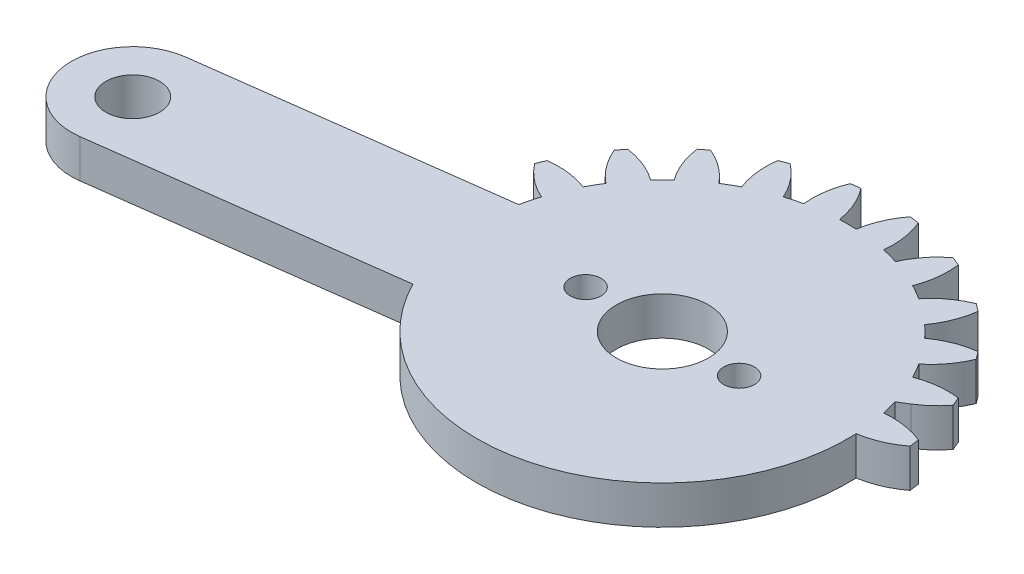
SolidWorks part; units mm, degrees
ref_plane "Front Plane" through (0, 0, 0) normal (0, 0, 1) x (1, 0, 0)
ref_plane "Top Plane" through (0, 0, 0) normal (0, 1, 0) x (1, 0, 0)
ref_plane "Right Plane" through (0, 0, 0) normal (1, 0, 0) x (0, 0, -1)
sketch "Sketch1" plane through (0, 0, 0) normal (0, 1, 0) x (1, 0, 0)
  line L0 (20.6437, 4) -> (2.0816, 4)
  line L1 (2.0816, -4) -> (20.6437, -4)
  arc A0 (2.0816, 4) -> (3.5217, 5.3071) centre (-0.7683, 8.5867) ccw
  arc A1 (3.5217, 5.3071) -> (3.2829, 5.8838) centre (-10.1063, 0) ccw
  arc A2 (3.2829, 5.8838) -> (0.6271, 5.5703) centre (2.5684, 0.5313) ccw
  arc A3 (0.6271, 5.5703) -> (0.0844, 6.5103) centre (-10.1063, 0) ccw
  arc A4 (0.0844, 6.5103) -> (1.6838, 8.6535) centre (-3.3089, 10.711) ccw
  arc A5 (1.6838, 8.6535) -> (1.3038, 9.1487) centre (-10.1063, 0) ccw
  arc A6 (1.3038, 9.1487) -> (-1.1803, 8.1585) centre (1.999, 3.7936) ccw
  arc A7 (-1.1803, 8.1585) -> (-1.9479, 8.926) centre (-10.1063, 0) ccw
  arc A8 (-1.9479, 8.926) -> (-0.9576, 11.4102) centre (-6.3127, 12.1053) ccw
  arc A9 (-0.9576, 11.4102) -> (-1.4528, 11.7901) centre (-10.1063, 0) ccw
  arc A10 (-1.4528, 11.7901) -> (-3.596, 10.1907) centre (0.6046, 6.7975) ccw
  arc A11 (-3.596, 10.1907) -> (-4.5361, 10.7334) centre (-10.1063, 0) ccw
  arc A12 (-4.5361, 10.7334) -> (-4.2225, 13.3892) centre (-9.5751, 12.6747) ccw
  arc A13 (-4.2225, 13.3892) -> (-4.7992, 13.6281) centre (-10.1063, 0) ccw
  arc A14 (-4.7992, 13.6281) -> (-6.4554, 11.5285) centre (-1.5196, 9.3381) ccw
  arc A15 (-6.4554, 11.5285) -> (-7.5039, 11.8094) centre (-10.1063, 0) ccw
  arc A16 (-7.5039, 11.8094) -> (-7.8884, 14.4558) centre (-12.8736, 12.3803) ccw
  arc A17 (-7.8884, 14.4558) -> (-8.5072, 14.5373) centre (-10.1063, 0) ccw
  arc A18 (-8.5072, 14.5373) -> (-9.5636, 12.0806) centre (-4.2291, 11.2423) ccw
  arc A19 (-9.5636, 12.0806) -> (-10.6491, 12.0806) centre (-10.1063, 0) ccw
  arc A20 (-10.6491, 12.0806) -> (-11.7054, 14.5373) centre (-15.9836, 11.2423) ccw
  arc A21 (-11.7054, 14.5373) -> (-12.3243, 14.4558) centre (-10.1063, 0) ccw
  arc A22 (-12.3243, 14.4558) -> (-12.7088, 11.8094) centre (-7.3391, 12.3803) ccw
  arc A23 (-12.7088, 11.8094) -> (-13.7573, 11.5285) centre (-10.1063, 0) ccw
  arc A24 (-13.7573, 11.5285) -> (-15.4135, 13.6281) centre (-18.6931, 9.3381) ccw
  arc A25 (-15.4135, 13.6281) -> (-15.9901, 13.3892) centre (-10.1063, 0) ccw
  arc A26 (-15.9901, 13.3892) -> (-15.6766, 10.7334) centre (-10.6376, 12.6747) ccw
  arc A27 (-15.6766, 10.7334) -> (-16.6166, 10.1907) centre (-10.1063, 0) ccw
  arc A28 (-16.6166, 10.1907) -> (-18.7599, 11.7901) centre (-20.8173, 6.7975) ccw
  arc A29 (-18.7599, 11.7901) -> (-19.255, 11.4102) centre (-10.1063, 0) ccw
  arc A30 (-19.255, 11.4102) -> (-18.2648, 8.926) centre (-13.9, 12.1053) ccw
  arc A31 (-18.2648, 8.926) -> (-19.0324, 8.1585) centre (-10.1063, 0) ccw
  arc A32 (-19.0324, 8.1585) -> (-21.5165, 9.1487) centre (-22.2117, 3.7936) ccw
  arc A33 (-21.5165, 9.1487) -> (-21.8965, 8.6535) centre (-10.1063, 0) ccw
  arc A34 (-21.8965, 8.6535) -> (-20.2971, 6.5103) centre (-16.9038, 10.711) ccw
  arc A35 (-20.2971, 6.5103) -> (-20.8398, 5.5703) centre (-10.1063, 0) ccw
  arc A36 (-20.8398, 5.5703) -> (-23.4956, 5.8838) centre (-22.7811, 0.5313) ccw
  arc A37 (-23.4956, 5.8838) -> (-23.7344, 5.3071) centre (-10.1063, 0) ccw
  arc A38 (-23.7344, 5.3071) -> (-21.6348, 3.6509) centre (-19.4444, 8.5867) ccw
  arc A39 (-21.6348, 3.6509) -> (-21.9157, 2.6025) centre (-10.1063, 0) ccw
  arc A40 (-21.9157, 2.6025) -> (-24.5622, 2.2179) centre (-22.4867, -2.7673) ccw
  arc A41 (-24.5622, 2.2179) -> (-24.6437, 1.5991) centre (-10.1063, 0) ccw
  arc A42 (-24.6437, 1.5991) -> (-22.1869, 0.5427) centre (-21.3486, 5.8773) ccw
  arc A43 (-22.1869, 0.5427) -> (-22.1869, -0.5427) centre (-10.1063, 0) ccw
  arc A44 (-22.1869, -0.5427) -> (-24.6437, -1.5991) centre (-21.3486, -5.8773) ccw
  arc A45 (-24.6437, -1.5991) -> (-24.5622, -2.2179) centre (-10.1063, 0) ccw
  arc A46 (-24.5622, -2.2179) -> (-21.9157, -2.6025) centre (-22.4867, 2.7673) ccw
  arc A47 (-21.9157, -2.6025) -> (-21.6348, -3.6509) centre (-10.1063, 0) ccw
  arc A48 (-21.6348, -3.6509) -> (-23.7344, -5.3071) centre (-19.4444, -8.5867) ccw
  arc A49 (-23.7344, -5.3071) -> (-23.4956, -5.8838) centre (-10.1063, 0) ccw
  arc A50 (-23.4956, -5.8838) -> (-20.8398, -5.5703) centre (-22.7811, -0.5313) ccw
  arc A51 (-20.8398, -5.5703) -> (-20.2971, -6.5103) centre (-10.1063, 0) ccw
  arc A52 (-20.2971, -6.5103) -> (-21.8965, -8.6535) centre (-16.9038, -10.711) ccw
  arc A53 (-21.8965, -8.6535) -> (-21.5165, -9.1487) centre (-10.1063, 0) ccw
  arc A54 (-21.5165, -9.1487) -> (-19.0324, -8.1585) centre (-22.2117, -3.7936) ccw
  arc A55 (-19.0324, -8.1585) -> (-18.2648, -8.926) centre (-10.1063, 0) ccw
  arc A56 (-18.2648, -8.926) -> (-19.255, -11.4102) centre (-13.9, -12.1053) ccw
  arc A57 (-19.255, -11.4102) -> (-18.7599, -11.7901) centre (-10.1063, 0) ccw
  arc A58 (-18.7599, -11.7901) -> (-16.6166, -10.1907) centre (-20.8173, -6.7975) ccw
  arc A59 (-16.6166, -10.1907) -> (-15.6766, -10.7334) centre (-10.1063, 0) ccw
  arc A60 (-15.6766, -10.7334) -> (-15.9901, -13.3892) centre (-10.6376, -12.6747) ccw
  arc A61 (-15.9901, -13.3892) -> (-15.4135, -13.6281) centre (-10.1063, 0) ccw
  arc A62 (-15.4135, -13.6281) -> (-13.7573, -11.5285) centre (-18.6931, -9.3381) ccw
  arc A63 (-13.7573, -11.5285) -> (-12.7088, -11.8094) centre (-10.1063, 0) ccw
  arc A64 (-12.7088, -11.8094) -> (-12.3243, -14.4558) centre (-7.3391, -12.3803) ccw
  arc A65 (-12.3243, -14.4558) -> (-11.7054, -14.5373) centre (-10.1063, 0) ccw
  arc A66 (-11.7054, -14.5373) -> (-10.6491, -12.0806) centre (-15.9836, -11.2423) ccw
  arc A67 (-10.6491, -12.0806) -> (-9.5636, -12.0806) centre (-10.1063, 0) ccw
  arc A68 (-9.5636, -12.0806) -> (-8.5072, -14.5373) centre (-4.2291, -11.2423) ccw
  arc A69 (-8.5072, -14.5373) -> (-7.8884, -14.4558) centre (-10.1063, 0) ccw
  arc A70 (-7.8884, -14.4558) -> (-7.5039, -11.8094) centre (-12.8736, -12.3803) ccw
  arc A71 (-7.5039, -11.8094) -> (-6.4554, -11.5285) centre (-10.1063, 0) ccw
  arc A72 (-6.4554, -11.5285) -> (-4.7992, -13.6281) centre (-1.5196, -9.3381) ccw
  arc A73 (-4.7992, -13.6281) -> (-4.2225, -13.3892) centre (-10.1063, 0) ccw
  arc A74 (-4.2225, -13.3892) -> (-4.5361, -10.7334) centre (-9.5751, -12.6747) ccw
  arc A75 (-4.5361, -10.7334) -> (-3.596, -10.1907) centre (-10.1063, 0) ccw
  arc A76 (-3.596, -10.1907) -> (-1.4528, -11.7901) centre (0.6046, -6.7975) ccw
  arc A77 (-1.4528, -11.7901) -> (-0.9576, -11.4102) centre (-10.1063, 0) ccw
  arc A78 (-0.9576, -11.4102) -> (-1.9479, -8.926) centre (-6.3127, -12.1053) ccw
  arc A79 (-1.9479, -8.926) -> (-1.1803, -8.1585) centre (-10.1063, 0) ccw
  arc A80 (-1.1803, -8.1585) -> (1.3038, -9.1487) centre (1.999, -3.7936) ccw
  arc A81 (1.3038, -9.1487) -> (1.6838, -8.6535) centre (-10.1063, 0) ccw
  arc A82 (1.6838, -8.6535) -> (0.0844, -6.5103) centre (-3.3089, -10.711) ccw
  arc A83 (0.0844, -6.5103) -> (0.6271, -5.5703) centre (-10.1063, 0) ccw
  arc A84 (0.6271, -5.5703) -> (3.2829, -5.8838) centre (2.5684, -0.5313) ccw
  arc A85 (3.2829, -5.8838) -> (3.5217, -5.3071) centre (-10.1063, 0) ccw
  arc A86 (3.5217, -5.3071) -> (2.0816, -4) centre (-0.7683, -8.5867) ccw
  arc A87 (20.6437, -4) -> (20.6437, 4) centre (20.6437, 0) ccw
  circle A88 centre (-10.1063, 0) radius 1.5
  circle A89 centre (20.6437, 0) radius 1.5
  dimension "D1" = 3
  dimension "D2" = 3
extrude "Boss-Extrude1" add sketch "Sketch1" along normal blind 2.5
sketch "Sketch3" plane through (0, 2.5, 0) normal (0, 1, 0) x (1, 0, 0)
  line L0 (-10.1063, 0) -> (-40.8563, 0) construction
  line L1 (-10.1063, 0) -> (-40.5933, -4.0137)
  line L2 (-10.6284, 3.9658) -> (-41.1154, -0.0479)
  line L3 (-9.5842, -3.9658) -> (-40.0712, -7.9795)
  line L4 (-10.1063, 0) -> (-4.5096, 13.5117) construction
  line L5 (-10.1063, 0) -> (-8.1974, 14.4999) construction
  circle A0 centre (-10.1063, 0) radius 1.5
  circle A1 centre (20.6437, 0) radius 1.5 construction
  circle A2 centre (20.6437, 0) radius 1.5
  circle A3 centre (-40.5933, -4.0137) radius 1.75
  circle A4 centre (-40.5933, -4.0137) radius 4
  circle A5 centre (-10.1063, 0) radius 4
  arc A6 (-4.2225, 13.3892) -> (-4.7992, 13.6281) centre (-10.1063, 0) ccw construction
  arc A7 (-7.8884, 14.4558) -> (-8.5072, 14.5373) centre (-10.1063, 0) ccw construction
  dimension "D2" = 3
  dimension "D5" = 3.5
  dimension "D6" = 8
  dimension "D7" = 8
  dimension "D1" = 30.75
  dimension "D4" = 7.5
extrude "Boss-Extrude2" add sketch "Sketch3" against normal blind 2.5 contours L0 A5 L2 | A5 L0 L2 A4 L1 | A4 A3 | A5 L1 A4 L3 | L0 A0 L1 A5 | A0 L0 A5 L1 region at (-13.19, 2.5, -2.3662) region at (-25.0786, 2.5, 4.0667) region at (-25.621, 2.5, -0.053) region at (-36.7147, 2.5, 3.7595)
sketch "Sketch4" plane through (0, 2.5, 0) normal (0, 1, 0) x (1, 0, 0)
  line L0 (20.6437, 4) -> (2.0816, 4) construction
  line L1 (2.0816, -4) -> (20.6437, -4) construction
  line L2 (20.6437, 4) -> (2.0816, 4)
  line L3 (2.0816, -4) -> (20.6437, -4)
  line L4 (2.0816, 4) -> (1.4381, 3.6001)
  line L5 (-21.6245, -5.5509) -> (-20.8986, -5.4553)
  line L6 (-10.1063, 0) -> (0.0844, 6.5103) construction
  line L7 (-10.1063, 0) -> (1.9742, 0.5427) construction
  line L8 (-24.5755, 2.1296) -> (-41.1154, -0.0479)
  line L9 (-40.0712, -7.9795) -> (-23.5312, -5.8019)
  line L10 (2.0816, -4) -> (20.6437, -4)
  line L11 (2.0816, -4) -> (20.6437, -4)
  line L12 (-21.9429, 2.4762) -> (-41.1154, -0.0479)
  line L13 (-40.0712, -7.9795) -> (-21.6245, -5.5509)
  line L18 (20.6437, 4) -> (2.0816, 4)
  line L19 (20.6437, 4) -> (2.0816, 4)
  circle A0 centre (-10.1063, 0) radius 12.0927
  arc A1 (3.2829, 5.8838) -> (0.6271, 5.5703) centre (2.5684, 0.5313) ccw construction
  arc A2 (3.5217, 5.3071) -> (3.2829, 5.8838) centre (-10.1063, 0) ccw construction
  arc A3 (2.0816, 4) -> (3.5217, 5.3071) centre (-0.7683, 8.5867) ccw construction
  arc A4 (20.6437, -4) -> (20.6437, 4) centre (20.6437, 0) ccw construction
  arc A5 (3.5217, -5.3071) -> (2.0816, -4) centre (-0.7683, -8.5867) ccw construction
  arc A6 (3.2829, -5.8838) -> (3.5217, -5.3071) centre (-10.1063, 0) ccw construction
  arc A7 (0.6271, -5.5703) -> (3.2829, -5.8838) centre (2.5684, -0.5313) ccw construction
  arc A8 (3.2829, 5.8838) -> (0.6271, 5.5703) centre (2.5684, 0.5313) ccw
  arc A9 (3.5217, 5.3071) -> (3.2829, 5.8838) centre (-10.1063, 0) ccw
  arc A10 (2.0816, 4) -> (3.5217, 5.3071) centre (-0.7683, 8.5867) ccw
  arc A11 (20.6437, -4) -> (20.6437, 4) centre (20.6437, 0) ccw
  arc A12 (3.5217, -5.3071) -> (2.0816, -4) centre (-0.7683, -8.5867) ccw
  arc A13 (3.2829, -5.8838) -> (3.5217, -5.3071) centre (-10.1063, 0) ccw
  arc A14 (0.6271, -5.5703) -> (3.2829, -5.8838) centre (2.5684, -0.5313) ccw
  arc A15 (1.9742, 0.5427) -> (4.431, 1.5991) centre (1.1359, 5.8773) ccw
  arc A16 (4.3495, 2.2179) -> (1.7031, 2.6025) centre (2.274, -2.7673) ccw
  arc A17 (4.431, 1.5991) -> (4.3495, 2.2179) centre (-10.1063, 0) ccw
  arc A64 (-20.2971, -6.5103) -> (-21.8965, -8.6535) centre (-16.9038, -10.711) ccw
  arc A65 (-20.2971, -6.5103) -> (-21.8965, -8.6535) centre (-16.9038, -10.711) ccw
  arc A66 (-21.8965, -8.6535) -> (-21.5165, -9.1487) centre (-10.1063, 0) ccw
  arc A67 (-21.8965, -8.6535) -> (-21.5165, -9.1487) centre (-10.1063, 0) ccw
  arc A68 (-21.5165, -9.1487) -> (-19.0324, -8.1585) centre (-22.2117, -3.7936) ccw
  arc A69 (-21.5165, -9.1487) -> (-19.0324, -8.1585) centre (-22.2117, -3.7936) ccw
  arc A70 (-18.2648, -8.926) -> (-19.255, -11.4102) centre (-13.9, -12.1053) ccw
  arc A71 (-18.2648, -8.926) -> (-19.255, -11.4102) centre (-13.9, -12.1053) ccw
  arc A95 (-21.6348, 3.6509) -> (-21.9157, 2.6025) centre (-10.1063, 0) ccw
  arc A96 (-41.1154, -0.0479) -> (-40.0712, -7.9795) centre (-40.5933, -4.0137) ccw
  arc A100 (-19.0324, -8.1585) -> (-18.2648, -8.926) centre (-10.1063, 0) ccw
  arc A111 (-19.255, -11.4102) -> (-18.7599, -11.7901) centre (-10.1063, 0) ccw
  arc A112 (-19.255, -11.4102) -> (-18.7599, -11.7901) centre (-10.1063, 0) ccw
  arc A113 (-18.7599, -11.7901) -> (-16.6166, -10.1907) centre (-20.8173, -6.7975) ccw
  arc A114 (-18.7599, -11.7901) -> (-16.6166, -10.1907) centre (-20.8173, -6.7975) ccw
  arc A115 (-16.6166, -10.1907) -> (-15.6766, -10.7334) centre (-10.1063, 0) ccw
  arc A116 (-16.6166, -10.1907) -> (-15.6766, -10.7334) centre (-10.1063, 0) ccw
  arc A117 (-15.6766, -10.7334) -> (-15.9901, -13.3892) centre (-10.6376, -12.6747) ccw
  arc A118 (-15.6766, -10.7334) -> (-15.9901, -13.3892) centre (-10.6376, -12.6747) ccw
  arc A119 (-15.9901, -13.3892) -> (-15.4135, -13.6281) centre (-10.1063, 0) ccw
  arc A120 (-15.9901, -13.3892) -> (-15.4135, -13.6281) centre (-10.1063, 0) ccw
  arc A121 (-15.4135, -13.6281) -> (-13.7573, -11.5285) centre (-18.6931, -9.3381) ccw
  arc A122 (-15.4135, -13.6281) -> (-13.7573, -11.5285) centre (-18.6931, -9.3381) ccw
  arc A123 (-13.7573, -11.5285) -> (-12.7088, -11.8094) centre (-10.1063, 0) ccw
  arc A124 (-13.7573, -11.5285) -> (-12.7088, -11.8094) centre (-10.1063, 0) ccw
  arc A125 (-12.7088, -11.8094) -> (-12.3243, -14.4558) centre (-7.3391, -12.3803) ccw
  arc A126 (-12.7088, -11.8094) -> (-12.3243, -14.4558) centre (-7.3391, -12.3803) ccw
  arc A127 (-12.3243, -14.4558) -> (-11.7054, -14.5373) centre (-10.1063, 0) ccw
  arc A128 (-12.3243, -14.4558) -> (-11.7054, -14.5373) centre (-10.1063, 0) ccw
  arc A129 (-11.7054, -14.5373) -> (-10.6491, -12.0806) centre (-15.9836, -11.2423) ccw
  arc A130 (-11.7054, -14.5373) -> (-10.6491, -12.0806) centre (-15.9836, -11.2423) ccw
  arc A131 (-10.6491, -12.0806) -> (-9.5636, -12.0806) centre (-10.1063, 0) ccw
  arc A132 (-10.6491, -12.0806) -> (-9.5636, -12.0806) centre (-10.1063, 0) ccw
  arc A133 (2.0816, 4) -> (3.5217, 5.3071) centre (-0.7683, 8.5867) ccw
  arc A134 (3.5217, 5.3071) -> (3.2829, 5.8838) centre (-10.1063, 0) ccw
  arc A135 (3.2829, 5.8838) -> (0.6271, 5.5703) centre (2.5684, 0.5313) ccw
  arc A136 (0.6271, 5.5703) -> (0.0844, 6.5103) centre (-10.1063, 0) ccw
  arc A137 (0.0844, 6.5103) -> (1.6838, 8.6535) centre (-3.3089, 10.711) ccw
  arc A138 (1.6838, 8.6535) -> (1.3038, 9.1487) centre (-10.1063, 0) ccw
  arc A139 (1.3038, 9.1487) -> (-1.1803, 8.1585) centre (1.999, 3.7936) ccw
  arc A140 (-1.1803, 8.1585) -> (-1.9479, 8.926) centre (-10.1063, 0) ccw
  arc A141 (-1.9479, 8.926) -> (-0.9576, 11.4102) centre (-6.3127, 12.1053) ccw
  arc A142 (-0.9576, 11.4102) -> (-1.4528, 11.7901) centre (-10.1063, 0) ccw
  arc A143 (-1.4528, 11.7901) -> (-3.596, 10.1907) centre (0.6046, 6.7975) ccw
  arc A144 (-3.596, 10.1907) -> (-4.5361, 10.7334) centre (-10.1063, 0) ccw
  arc A145 (-4.5361, 10.7334) -> (-4.2225, 13.3892) centre (-9.5751, 12.6747) ccw
  arc A146 (-4.2225, 13.3892) -> (-4.7992, 13.6281) centre (-10.1063, 0) ccw
  arc A147 (-4.7992, 13.6281) -> (-6.4554, 11.5285) centre (-1.5196, 9.3381) ccw
  arc A148 (-6.4554, 11.5285) -> (-7.5039, 11.8094) centre (-10.1063, 0) ccw
  arc A149 (-7.5039, 11.8094) -> (-7.8884, 14.4558) centre (-12.8736, 12.3803) ccw
  arc A150 (-7.8884, 14.4558) -> (-8.5072, 14.5373) centre (-10.1063, 0) ccw
  arc A151 (-8.5072, 14.5373) -> (-9.5636, 12.0806) centre (-4.2291, 11.2423) ccw
  arc A152 (-9.5636, 12.0806) -> (-10.6491, 12.0806) centre (-10.1063, 0) ccw
  arc A153 (-10.6491, 12.0806) -> (-11.7054, 14.5373) centre (-15.9836, 11.2423) ccw
  arc A154 (-11.7054, 14.5373) -> (-12.3243, 14.4558) centre (-10.1063, 0) ccw
  arc A155 (-12.3243, 14.4558) -> (-12.7088, 11.8094) centre (-7.3391, 12.3803) ccw
  arc A156 (-12.7088, 11.8094) -> (-13.7573, 11.5285) centre (-10.1063, 0) ccw
  arc A157 (-13.7573, 11.5285) -> (-15.4135, 13.6281) centre (-18.6931, 9.3381) ccw
  arc A158 (-15.4135, 13.6281) -> (-15.9901, 13.3892) centre (-10.1063, 0) ccw
  arc A159 (-15.9901, 13.3892) -> (-15.6766, 10.7334) centre (-10.6376, 12.6747) ccw
  arc A160 (-15.6766, 10.7334) -> (-16.6166, 10.1907) centre (-10.1063, 0) ccw
  arc A161 (-16.6166, 10.1907) -> (-18.7599, 11.7901) centre (-20.8173, 6.7975) ccw
  arc A162 (-18.7599, 11.7901) -> (-19.255, 11.4102) centre (-10.1063, 0) ccw
  arc A163 (-19.255, 11.4102) -> (-18.2648, 8.926) centre (-13.9, 12.1053) ccw
  arc A164 (-18.2648, 8.926) -> (-19.0324, 8.1585) centre (-10.1063, 0) ccw
  arc A165 (-19.0324, 8.1585) -> (-21.5165, 9.1487) centre (-22.2117, 3.7936) ccw
  arc A166 (-21.5165, 9.1487) -> (-21.8965, 8.6535) centre (-10.1063, 0) ccw
  arc A167 (-21.8965, 8.6535) -> (-20.2971, 6.5103) centre (-16.9038, 10.711) ccw
  arc A168 (-20.2971, 6.5103) -> (-20.8398, 5.5703) centre (-10.1063, 0) ccw
  arc A169 (-20.8398, 5.5703) -> (-23.4956, 5.8838) centre (-22.7811, 0.5313) ccw
  arc A170 (-23.4956, 5.8838) -> (-23.7344, 5.3071) centre (-10.1063, 0) ccw
  arc A171 (-23.7344, 5.3071) -> (-21.6348, 3.6509) centre (-19.4444, 8.5867) ccw
  arc A172 (-21.6348, 3.6509) -> (-21.9157, 2.6025) centre (-10.1063, 0) ccw
  arc A173 (-9.5636, -12.0806) -> (-8.5072, -14.5373) centre (-4.2291, -11.2423) ccw
  arc A174 (-9.5636, -12.0806) -> (-8.5072, -14.5373) centre (-4.2291, -11.2423) ccw
  arc A175 (-8.5072, -14.5373) -> (-7.8884, -14.4558) centre (-10.1063, 0) ccw
  arc A176 (-41.1154, -0.0479) -> (-40.0712, -7.9795) centre (-40.5933, -4.0137) ccw
  arc A177 (-8.5072, -14.5373) -> (-7.8884, -14.4558) centre (-10.1063, 0) ccw
  arc A178 (-7.8884, -14.4558) -> (-7.5039, -11.8094) centre (-12.8736, -12.3803) ccw
  arc A179 (-7.8884, -14.4558) -> (-7.5039, -11.8094) centre (-12.8736, -12.3803) ccw
  arc A180 (-19.0324, -8.1585) -> (-18.2648, -8.926) centre (-10.1063, 0) ccw
  arc A181 (-7.5039, -11.8094) -> (-6.4554, -11.5285) centre (-10.1063, 0) ccw
  arc A182 (-7.5039, -11.8094) -> (-6.4554, -11.5285) centre (-10.1063, 0) ccw
  arc A183 (-6.4554, -11.5285) -> (-4.7992, -13.6281) centre (-1.5196, -9.3381) ccw
  arc A184 (-6.4554, -11.5285) -> (-4.7992, -13.6281) centre (-1.5196, -9.3381) ccw
  arc A185 (-4.7992, -13.6281) -> (-4.2225, -13.3892) centre (-10.1063, 0) ccw
  arc A186 (-4.7992, -13.6281) -> (-4.2225, -13.3892) centre (-10.1063, 0) ccw
  arc A187 (-4.2225, -13.3892) -> (-4.5361, -10.7334) centre (-9.5751, -12.6747) ccw
  arc A188 (-4.2225, -13.3892) -> (-4.5361, -10.7334) centre (-9.5751, -12.6747) ccw
  arc A189 (-4.5361, -10.7334) -> (-3.596, -10.1907) centre (-10.1063, 0) ccw
  arc A190 (-4.5361, -10.7334) -> (-3.596, -10.1907) centre (-10.1063, 0) ccw
  arc A191 (-3.596, -10.1907) -> (-1.4528, -11.7901) centre (0.6046, -6.7975) ccw
  arc A192 (-3.596, -10.1907) -> (-1.4528, -11.7901) centre (0.6046, -6.7975) ccw
  arc A193 (-1.4528, -11.7901) -> (-0.9576, -11.4102) centre (-10.1063, 0) ccw
  arc A194 (-1.4528, -11.7901) -> (-0.9576, -11.4102) centre (-10.1063, 0) ccw
  arc A195 (-0.9576, -11.4102) -> (-1.9479, -8.926) centre (-6.3127, -12.1053) ccw
  arc A196 (-0.9576, -11.4102) -> (-1.9479, -8.926) centre (-6.3127, -12.1053) ccw
  arc A197 (-1.9479, -8.926) -> (-1.1803, -8.1585) centre (-10.1063, 0) ccw
  arc A198 (-1.9479, -8.926) -> (-1.1803, -8.1585) centre (-10.1063, 0) ccw
  arc A199 (-1.1803, -8.1585) -> (1.3038, -9.1487) centre (1.999, -3.7936) ccw
  arc A200 (-1.1803, -8.1585) -> (1.3038, -9.1487) centre (1.999, -3.7936) ccw
  arc A201 (1.3038, -9.1487) -> (1.6838, -8.6535) centre (-10.1063, 0) ccw
  arc A202 (1.3038, -9.1487) -> (1.6838, -8.6535) centre (-10.1063, 0) ccw
  arc A203 (1.6838, -8.6535) -> (0.0844, -6.5103) centre (-3.3089, -10.711) ccw
  arc A204 (1.6838, -8.6535) -> (0.0844, -6.5103) centre (-3.3089, -10.711) ccw
  arc A205 (0.0844, -6.5103) -> (0.6271, -5.5703) centre (-10.1063, 0) ccw
  arc A206 (0.0844, -6.5103) -> (0.6271, -5.5703) centre (-10.1063, 0) ccw
  arc A207 (0.6271, -5.5703) -> (3.2829, -5.8838) centre (2.5684, -0.5313) ccw
  arc A208 (0.6271, -5.5703) -> (3.2829, -5.8838) centre (2.5684, -0.5313) ccw
  arc A209 (3.2829, -5.8838) -> (3.5217, -5.3071) centre (-10.1063, 0) ccw
  arc A210 (3.2829, -5.8838) -> (3.5217, -5.3071) centre (-10.1063, 0) ccw
  arc A211 (3.5217, -5.3071) -> (2.0816, -4) centre (-0.7683, -8.5867) ccw
  arc A212 (3.5217, -5.3071) -> (2.0816, -4) centre (-0.7683, -8.5867) ccw
  arc A213 (2.0816, 4) -> (3.5217, 5.3071) centre (-0.7683, 8.5867) ccw
  arc A214 (3.5217, 5.3071) -> (3.2829, 5.8838) centre (-10.1063, 0) ccw
  arc A215 (3.2829, 5.8838) -> (0.6271, 5.5703) centre (2.5684, 0.5313) ccw
  arc A216 (0.6271, 5.5703) -> (0.0844, 6.5103) centre (-10.1063, 0) ccw
  arc A217 (0.0844, 6.5103) -> (1.6838, 8.6535) centre (-3.3089, 10.711) ccw
  arc A218 (1.6838, 8.6535) -> (1.3038, 9.1487) centre (-10.1063, 0) ccw
  arc A219 (1.3038, 9.1487) -> (-1.1803, 8.1585) centre (1.999, 3.7936) ccw
  arc A220 (-1.1803, 8.1585) -> (-1.9479, 8.926) centre (-10.1063, 0) ccw
  arc A221 (-1.9479, 8.926) -> (-0.9576, 11.4102) centre (-6.3127, 12.1053) ccw
  arc A222 (-0.9576, 11.4102) -> (-1.4528, 11.7901) centre (-10.1063, 0) ccw
  arc A223 (-1.4528, 11.7901) -> (-3.596, 10.1907) centre (0.6046, 6.7975) ccw
  arc A224 (-3.596, 10.1907) -> (-4.5361, 10.7334) centre (-10.1063, 0) ccw
  arc A225 (-4.5361, 10.7334) -> (-4.2225, 13.3892) centre (-9.5751, 12.6747) ccw
  arc A226 (-4.2225, 13.3892) -> (-4.7992, 13.6281) centre (-10.1063, 0) ccw
  arc A227 (-4.7992, 13.6281) -> (-6.4554, 11.5285) centre (-1.5196, 9.3381) ccw
  arc A228 (-6.4554, 11.5285) -> (-7.5039, 11.8094) centre (-10.1063, 0) ccw
  arc A229 (-7.5039, 11.8094) -> (-7.8884, 14.4558) centre (-12.8736, 12.3803) ccw
  arc A230 (-7.8884, 14.4558) -> (-8.5072, 14.5373) centre (-10.1063, 0) ccw
  arc A231 (-8.5072, 14.5373) -> (-9.5636, 12.0806) centre (-4.2291, 11.2423) ccw
  arc A232 (-9.5636, 12.0806) -> (-10.6491, 12.0806) centre (-10.1063, 0) ccw
  arc A233 (-10.6491, 12.0806) -> (-11.7054, 14.5373) centre (-15.9836, 11.2423) ccw
  arc A234 (-11.7054, 14.5373) -> (-12.3243, 14.4558) centre (-10.1063, 0) ccw
  arc A235 (-12.3243, 14.4558) -> (-12.7088, 11.8094) centre (-7.3391, 12.3803) ccw
  arc A236 (-12.7088, 11.8094) -> (-13.7573, 11.5285) centre (-10.1063, 0) ccw
  arc A237 (-13.7573, 11.5285) -> (-15.4135, 13.6281) centre (-18.6931, 9.3381) ccw
  arc A238 (-15.4135, 13.6281) -> (-15.9901, 13.3892) centre (-10.1063, 0) ccw
  arc A239 (-15.9901, 13.3892) -> (-15.6766, 10.7334) centre (-10.6376, 12.6747) ccw
  arc A240 (-15.6766, 10.7334) -> (-16.6166, 10.1907) centre (-10.1063, 0) ccw
  arc A241 (-16.6166, 10.1907) -> (-18.7599, 11.7901) centre (-20.8173, 6.7975) ccw
  arc A242 (-18.7599, 11.7901) -> (-19.255, 11.4102) centre (-10.1063, 0) ccw
  arc A243 (-19.255, 11.4102) -> (-18.2648, 8.926) centre (-13.9, 12.1053) ccw
  arc A244 (-18.2648, 8.926) -> (-19.0324, 8.1585) centre (-10.1063, 0) ccw
  arc A245 (-19.0324, 8.1585) -> (-21.5165, 9.1487) centre (-22.2117, 3.7936) ccw
  arc A246 (-21.5165, 9.1487) -> (-21.8965, 8.6535) centre (-10.1063, 0) ccw
  arc A247 (-21.8965, 8.6535) -> (-20.2971, 6.5103) centre (-16.9038, 10.711) ccw
  arc A248 (-20.2971, 6.5103) -> (-20.8398, 5.5703) centre (-10.1063, 0) ccw
  arc A249 (-20.8398, 5.5703) -> (-23.4956, 5.8838) centre (-22.7811, 0.5313) ccw
  arc A250 (-23.4956, 5.8838) -> (-23.7344, 5.3071) centre (-10.1063, 0) ccw
  arc A251 (-23.7344, 5.3071) -> (-21.6348, 3.6509) centre (-19.4444, 8.5867) ccw
  arc A252 (20.6437, -4) -> (20.6437, 4) centre (20.6437, 0) ccw
  arc A253 (20.6437, -4) -> (20.6437, 4) centre (20.6437, 0) ccw
  arc A254 (-21.9157, 2.6025) -> (-24.5622, 2.2179) centre (-22.4867, -2.7673) ccw
  arc A255 (-21.9157, 2.6025) -> (-24.5622, 2.2179) centre (-22.4867, -2.7673) ccw
  arc A256 (-24.5622, 2.2179) -> (-24.5755, 2.1296) centre (-10.1063, 0) ccw
  arc A257 (-24.5622, 2.2179) -> (-24.5755, 2.1296) centre (-10.1063, 0) ccw
  arc A258 (-23.5312, -5.8019) -> (-23.4956, -5.8838) centre (-10.1063, 0) ccw
  arc A259 (-23.5312, -5.8019) -> (-23.4956, -5.8838) centre (-10.1063, 0) ccw
  arc A260 (-23.4956, -5.8838) -> (-20.8398, -5.5703) centre (-22.7811, -0.5313) ccw
  arc A261 (-23.4956, -5.8838) -> (-20.8398, -5.5703) centre (-22.7811, -0.5313) ccw
  arc A262 (-20.8398, -5.5703) -> (-20.2971, -6.5103) centre (-10.1063, 0) ccw
  arc A263 (-20.8398, -5.5703) -> (-20.2971, -6.5103) centre (-10.1063, 0) ccw
  point P40 (-10.1063, 0)
  dimension "D2" = 24.1855
  dimension "D4" = 30
  dimension "D1" = 0
  dimension "D3" = 2
extrude "Cut-Extrude1" cut sketch "Sketch4" against normal blind 4 contours A67 A69 A0 L5 A65 | A112 A114 A0 A71 | A120 A122 A0 A118 | A128 A130 A0 A126 | A177 A179 A0 A174 | A186 A188 A0 A184 | A194 A196 A0 A192 | A202 A204 A0 A200 | A255 A257 L12 A0 | L13 A259 A261 A0 L5 | A0 A14 A13 A12 L3 A11 L2 L4 region at (12.7894, 2.5, 0.1545) region at (0.3325, 2.5, 8.01) region at (-2.0963, 2.5, 10.4389) region at (-5.071, 2.5, 12.1563) region at (-8.3889, 2.5, 13.0454) region at (-11.8238, 2.5, 13.0454) region at (-15.1417, 2.5, 12.1563) region at (-18.1164, 2.5, 10.4389) region at (-20.5452, 2.5, 8.01) region at (-23.2126, 2.5, -2.4243) region at (-22.1386, 2.5, 5.7339)
sketch "Sketch5" plane through (0, 2.5, 0) normal (0, 1, 0) x (1, 0, 0)
  circle A0 centre (-10.1063, 0) radius 3
  circle A1 centre (-5.1063, 0) radius 1
  circle A2 centre (-15.1063, 0) radius 1
  circle A3 centre (-10.1063, 0) radius 1.5 construction
  dimension "D1" = 6
  dimension "D2" = 2
  dimension "D3" = 2
  dimension "D4" = 5
  dimension "D5" = 10
extrude "Cut-Extrude2" cut sketch "Sketch5" against normal up to next contours A2 | A1 | A0 region at (-5.1063, 2.5, 0) region at (-15.1063, 2.5, 0)
